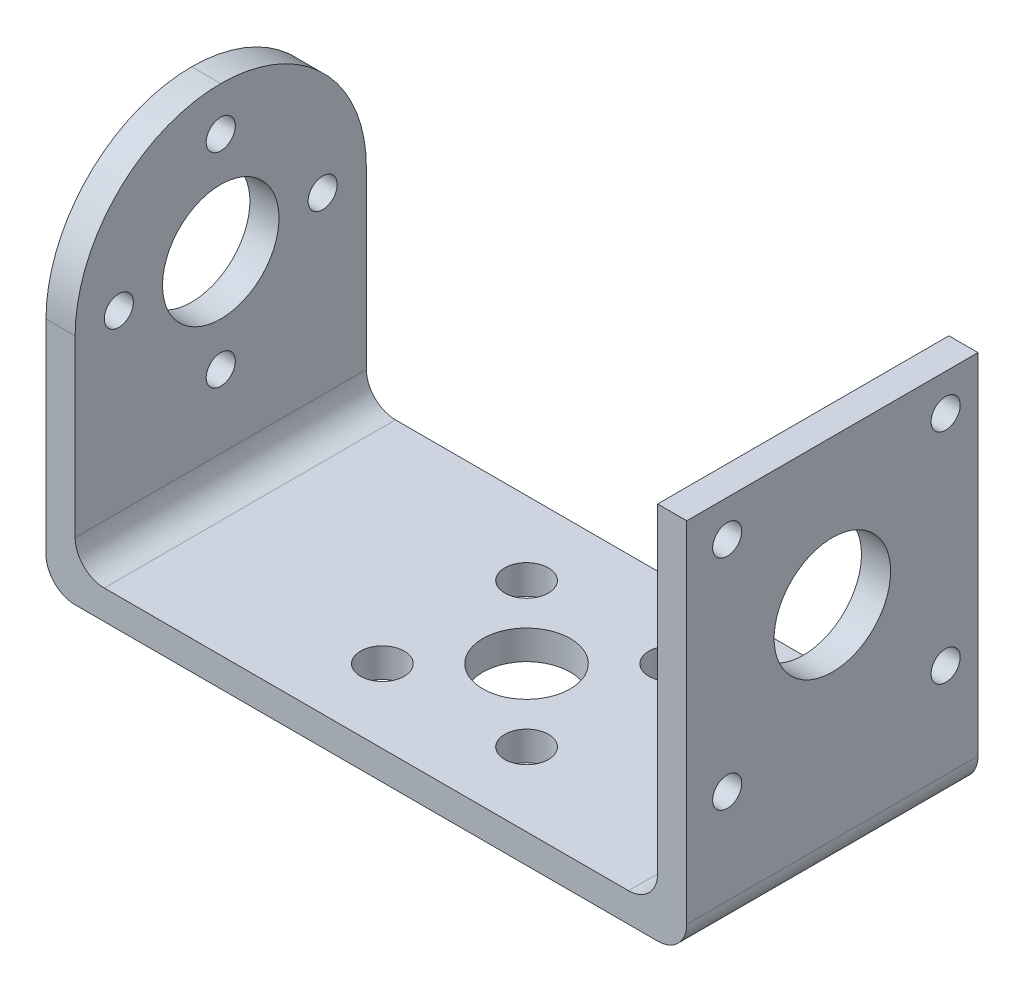
SolidWorks part; units mm, degrees
ref_plane "Спереди" through (0, 0, 0) normal (0, 0, 1) x (1, 0, 0)
ref_plane "Сверху" through (0, 0, 0) normal (0, 1, 0) x (1, 0, 0)
ref_plane "Справа" through (0, 0, 0) normal (1, 0, 0) x (0, 0, -1)
sketch "Sketch1" plane through (0, 0, 0) normal (0, 0, 1) x (1, 0, 0)
  line L0 (0, 0) -> (44, 0)
  line L1 (44, 0) -> (44, 26)
  line L2 (44, 26) -> (42, 26)
  line L3 (42, 26) -> (42, 2)
  line L4 (2, 2) -> (42, 2)
  line L5 (2, 2) -> (2, 26)
  line L6 (2, 26) -> (0, 26)
  line L7 (0, 26) -> (0, 0)
  dimension "D1" = 44
  dimension "D2" = 26
  dimension "D3" = 2
  dimension "D4" = 2
  dimension "D5" = 24
  dimension "D6" = 2
extrude "Основа" add sketch "Sketch1" along normal blind 20
sketch "Sketch2" plane through (0, 0, 0) normal (-1, 0, 0) x (0, 0, 1)
  line L0 (10, 16) -> (10, 23) construction
  line L1 (0, 0) -> (10, 0) construction
  line L2 (20, 0) -> (0, 0) construction
  line L3 (20, 26) -> (0, 26) construction
  line L5 (10, 0) -> (10, 16) construction
  line L6 (10, 16) -> (10, 9) construction
  circle A0 centre (10, 16) radius 4
  circle A1 centre (10, 23) radius 1
  circle A2 centre (17, 16) radius 1
  circle A3 centre (10, 9) radius 1
  circle A4 centre (3, 16) radius 1
  circle A5 centre (10, 16) radius 7 construction
  point P16 (10, 16)
  dimension "D1" = 8
  dimension "D4" = 2
  dimension "D2" = 14
  dimension "D5" = 10
  dimension "D3" = 4
extrude "Отверстия под ось и винты 1" cut sketch "Sketch2" against normal blind 2
sketch "Sketch3" plane through (44, 0, 0) normal (1, 0, 0) x (0, 0, -1)
  line L0 (-20, 26) -> (0, 26) construction
  line L1 (-17.2218, 23.5) -> (-2.2218, 23.5) construction
  line L2 (0, 26) -> (0, 6)
  line L3 (0, 0) -> (0, 26) construction
  line L4 (-2.2218, 23.5) -> (-2.2218, 8.5) construction
  line L5 (-2.2218, 8.5) -> (-17.2218, 8.5) construction
  line L6 (-17.2218, 8.5) -> (-17.2218, 23.5) construction
  circle A0 centre (-10, 16) radius 4
  circle A1 centre (-2.2218, 23.5) radius 1
  circle A2 centre (-2.2218, 8.5) radius 1
  circle A3 centre (-17.2218, 8.5) radius 1
  circle A4 centre (-17.2218, 23.5) radius 1
  dimension "D1" = 8
  dimension "D7" = 2
  dimension "D2" = 15
  dimension "D3" = 7.5
  dimension "D4" = 10
  dimension "D5" = 10
  dimension "D6" = 4
extrude "Отверстия под ось и винты 2" cut sketch "Sketch3" against normal blind 20 contours A4 | A0 | A1 | A2 | A3 region at (44, 16, 10) region at (44, 23.5, 2.2218) region at (44, 8.5, 2.2218) region at (44, 8.5, 17.2218) region at (44, 23.5, 17.2218)
sketch "Sketch4" plane through (0, 0, 0) normal (0, -1, 0) x (1, 0, 0)
  line L0 (0, 0) -> (46, 0) construction
  line L1 (23, 10) -> (23, 0)
  line L2 (23, 10) -> (27.9497, 5.0503) construction
  circle A0 centre (23, 10) radius 3
  circle A1 centre (18.0503, 5.0503) radius 1.5
  circle A2 centre (27.9497, 5.0503) radius 1.5
  circle A3 centre (18.0503, 14.9497) radius 1.5
  circle A4 centre (27.9497, 14.9497) radius 1.5
  circle A5 centre (23, 10) radius 7 construction
  point P11 (23, 10)
  point P17 (23, 10)
  dimension "D1" = 6
  dimension "D4" = 45
  dimension "D6" = 4
  dimension "D5" = 3
  dimension "D7" = 14
  dimension "D2" = 10
  dimension "D3" = 23
extrude "Отверстия под крепёж" cut sketch "Sketch4" against normal blind 2 contours A0 | A4 | A3 | A1 | A2 region at (25.0613, 0, 7.9387) region at (18.0503, 0, 5.0503) region at (27.9497, 0, 5.0503) region at (18.0503, 0, 14.9497) region at (27.9497, 0, 14.9497)
fillet "Fillet1" radius 10 2 edges at (1, 26, 0) (1, 26, 20)
fillet "Fillet2" radius 2 4 edges at (0, 0, 10) (42, 2, 10) (2, 2, 10) (44, 0, 10)
